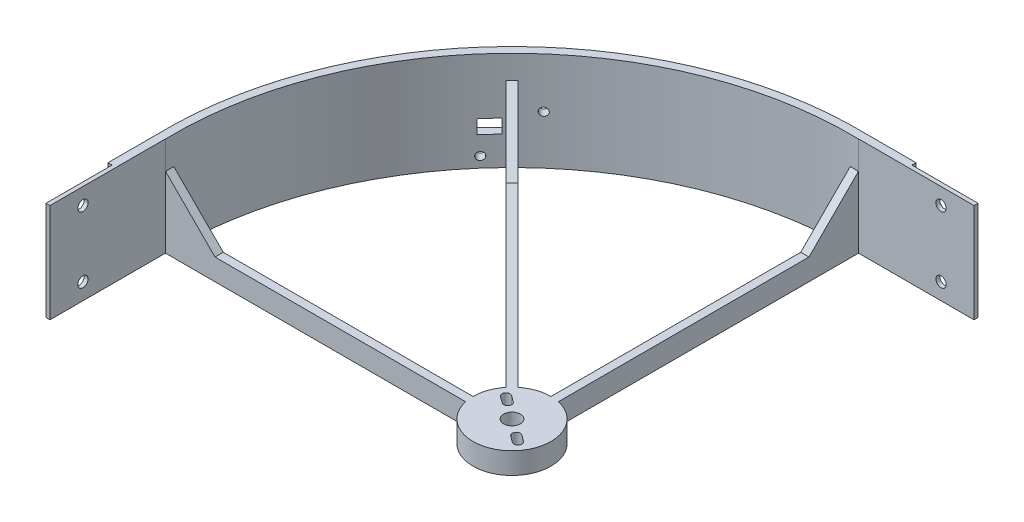
SolidWorks part; units mm, degrees
note: The reader was unsure of these and kept them because the rebuilt part matched: shared geometry of "Sketch1<6>", "Sketch1<7>", "Sketch21<3>".
material "ABS"
ref_plane "Front Plane" through (0, 0, 0) normal (0, 0, 1) x (1, 0, 0)
ref_plane "Top Plane" through (0, 0, 0) normal (0, 1, 0) x (1, 0, 0)
ref_plane "Right Plane" through (0, 0, 0) normal (1, 0, 0) x (0, 0, -1)
sketch "Sketch1" plane through (0, 0, 0) normal (0, 1, 0) x (1, 0, 0)
  line L0 (0, 130.175) -> (0, 9.3426)
  line L1 (3.175, 9.3426) -> (3.175, 130.1363)
  line L2 (-92.0476, 92.0476) -> (0, 0) construction
  line L3 (-90.9182, 93.1633) -> (-5.7657, 8.0107)
  line L4 (-9.7388, -3.175) -> (-130.1363, -3.175)
  line L5 (-130.175, 0) -> (-9.3426, 0)
  line L6 (3.175, 9.3426) -> (3.175, 130.1363)
  line L7 (3.175, 130.1363) -> (3.175, 133.3122)
  line L8 (-130.1363, -3.175) -> (-133.3122, -3.175)
  line L9 (0, 0) -> (-130.175, 0) construction
  line L10 (-8.0089, 5.7638) -> (-93.1633, 90.9182)
  line L11 (0, 0) -> (0, 146.05) construction
  circle A0 centre (0, 0) radius 15
  arc A1 (3.175, 130.1363) -> (-130.1363, -3.175) centre (0, 0) ccw
  arc A2 (3.175, 133.3122) -> (-133.3122, -3.175) centre (0, 0) ccw
  point P21 (0, 0)
  dimension "D1" = 30
  dimension "D2" = 133.35
  dimension "D4" = 3.175
  dimension "D6" = 1.5875
  dimension "D3" = 3.175
  dimension "D7" = 1.5875
  dimension "D5" = 3.175
extrude "Boss-Extrude2" add sketch "Sketch1" along normal blind 8.255 contours A0
extrude "Boss-Extrude3" add sketch "Sketch1<6>" along normal blind 8.255
sketch "Sketch1<6>" plane through (0, 0, 0) normal (0, 1, 0) x (1, 0, 0) same geometry as "Sketch1"
extrude "Boss-Extrude4" add sketch "Sketch1<7>" along normal blind 38.1 contours L7 A2 L8 A1
sketch "Sketch1<7>" plane through (0, 0, 0) normal (0, 1, 0) x (1, 0, 0) same geometry as "Sketch1"
ref_plane "Plane1" through (-63.4806, 0, -63.4806) normal (0.7071, 0, 0.7071) x (0.7071, 0, -0.7071)
sketch "Sketch5" plane through (0, 8.255, 0) normal (0, 1, 0) x (1, 0, 0)
  line L0 (0, 0) -> (-92.0476, 92.0476) construction
  line L1 (0, 0) -> (15.8128, 15.8128) construction
  line L2 (-8.7797, 6.4967) -> (0, 0) construction
  line L3 (-6.3296, 4.6836) -> (-8.7797, 6.4967) construction
  line L4 (-7.2361, 3.4586) -> (-9.6862, 5.2716)
  line L5 (-5.4231, 5.9087) -> (-7.8732, 7.7217)
  line L6 (0, 0) -> (3.6216, 4.8943) construction
  line L7 (6.3296, -4.6836) -> (8.7797, -6.4967) construction
  line L8 (5.4231, -5.9087) -> (7.8732, -7.7217)
  line L9 (7.2361, -3.4586) -> (9.6862, -5.2716)
  line L10 (-90.9182, 93.1633) -> (-9.4245, 11.6696) construction
  arc A0 (5.4231, -5.9087) -> (7.2361, -3.4586) centre (6.3296, -4.6836) cw
  arc A1 (-7.2361, 3.4586) -> (-5.4231, 5.9087) centre (-6.3296, 4.6836) ccw
  arc A2 (-7.8732, 7.7217) -> (-9.6862, 5.2716) centre (-8.7797, 6.4967) ccw
  arc A3 (9.6862, -5.2716) -> (7.8732, -7.7217) centre (8.7797, -6.4967) cw
  circle A6 centre (0, 0) radius 3.25
  point P8 (-7.5546, 5.5901)
  point P17 (7.5546, -5.5901)
  point P18 (0, 0)
  dimension "D3" = 3.048
  dimension "D1" = 7.874
  dimension "D2" = 3.048
  dimension "D4" = 8.5
extrude "Cut-Extrude3" cut sketch "Sketch5" against normal blind 63.5
sketch "Sketch6" plane through (0, 0, 3.175) normal (0, 0, 1) x (1, 0, 0)
  line L0 (-14.6601, 0) -> (-133.3122, 0) construction
  line L1 (-130.1363, 38.1) -> (-131.7242, 38.1)
  line L2 (-130.1363, 38.1) -> (-130.1363, 0)
  line L3 (-130.1363, 0) -> (-131.7242, 0)
  line L4 (-131.7242, 38.1) -> (-131.7242, 0)
  line L5 (-130.1363, 38.1) -> (-133.3122, 38.1) construction
  point P7 (-131.7242, 38.1)
sketch "Sketch7" plane through (3.175, 0, 0) normal (1, 0, 0) x (0, 0, -1)
  line L0 (14.6601, 0) -> (133.3122, 0) construction
  line L1 (130.1363, 38.1) -> (131.7242, 38.1)
  line L2 (130.1363, 38.1) -> (130.1363, 0)
  line L3 (130.1363, 0) -> (131.7242, 0)
  line L4 (131.7242, 38.1) -> (131.7242, 0)
  line L5 (130.1363, 38.1) -> (133.3122, 38.1) construction
  line L6 (130.1363, 38.1) -> (130.1363, 8.255) construction
  point P7 (131.7242, 38.1)
ref_plane "Plane2" through (0, 0, 0) normal (0, 0, -1) x (-1, 0, 0)
sketch "Sketch10" plane through (0, 0, 0) normal (0, 0, -1) x (-1, 0, 0)
  line L0 (130.175, 27.305) -> (130.175, 8.255)
  line L4 (130.175, 8.255) -> (130.175, 38.1) construction
  line L5 (130.175, 8.255) -> (111.125, 8.255)
  line L6 (130.175, 8.255) -> (15, 8.255) construction
  line L7 (111.125, 8.255) -> (130.175, 27.305)
  dimension "D1" = 19.05
  dimension "D2" = 45
extrude "Boss-Extrude9" add sketch "Sketch10" against normal blind 3.175
ref_plane "Plane3" through (1.1225, 0, -1.1225) normal (0.7071, 0, -0.7071) x (-0.7071, 0, -0.7071)
ref_plane "Plane4" through (0, 0, 0) normal (-1, 0, 0) x (0, 0, 1)
sketch "Sketch13" plane through (0, 0, 0) normal (-1, 0, 0) x (0, 0, 1)
  line L0 (-130.175, 27.305) -> (-111.125, 8.255)
  line L1 (-130.175, 27.305) -> (-130.175, 8.255)
  line L2 (-130.175, 8.255) -> (-15, 8.255) construction
  line L3 (-130.175, 8.255) -> (-111.125, 8.255)
  line L4 (-130.175, 38.1) -> (-130.175, 8.255) construction
  dimension "D1" = 45
  dimension "D2" = 19.05
extrude "Boss-Extrude11" add sketch "Sketch13" against normal blind 3.175
sketch "Sketch14" plane through (1.1225, 0, -1.1225) normal (0.7071, 0, -0.7071) x (-0.7071, 0, -0.7071)
  line L0 (133.3403, 8.255) -> (111.1153, 8.255)
  line L1 (130.1653, 8.255) -> (14.9158, 8.255) construction
  line L2 (133.3403, 8.255) -> (133.3403, 32.3947)
  line L3 (133.3403, 32.3947) -> (111.1153, 8.255)
  dimension "D1" = 22.225
extrude "Boss-Extrude14" add sketch "Sketch14" against normal blind 3.175
ref_plane "Plane5" through (-131.7242, 0, 0) normal (-1, 0, 0) x (0, -1, 0)
sketch "Sketch15" plane through (-131.7242, 0, 0) normal (-1, 0, 0) x (0, -1, 0)
  line L1 (-38.1, 47.625) -> (0, 47.625)
  line L2 (-38.1, 47.625) -> (-38.1, 3.175)
  line L3 (-38.1, 3.175) -> (0, 3.175)
  line L4 (0, 47.625) -> (0, 3.175)
  dimension "D1" = 44.45
extrude "Boss-Extrude15" add sketch "Sketch15" against normal blind 1.524
ref_plane "Plane6" through (0, 0, -131.7242) normal (0, 0, -1) x (0, -1, 0)
sketch "Sketch16" plane through (0, 0, -131.7242) normal (0, 0, -1) x (0, -1, 0)
  line L1 (-38.1, -3.175) -> (0, -3.175)
  line L2 (-38.1, -3.175) -> (-38.1, -47.625)
  line L3 (-38.1, -47.625) -> (0, -47.625)
  line L4 (0, -3.175) -> (0, -47.625)
  dimension "D1" = 44.45
extrude "Boss-Extrude16" add sketch "Sketch16" against normal blind 1.524
sketch "Sketch17" plane through (0, 0, -131.7242) normal (0, 0, -1) x (-1, 0, 0)
  line L1 (-3.175, 38.1) -> (-47.625, 38.1) construction
  line L2 (19.05, 19.05) -> (-47.625, 19.05) construction
  line L3 (-47.625, 38.1) -> (-47.625, 0) construction
  circle A0 centre (-34.925, 31.75) radius 1.985
  circle A1 centre (-34.925, 6.35) radius 1.985
  dimension "D1" = 12.7
  dimension "D3" = 3.97
  dimension "D2" = 6.35
extrude "Cut-Extrude4" cut sketch "Sketch17" against normal blind 2.54
sketch "Sketch18" plane through (-131.7242, 0, 0) normal (-1, 0, 0) x (0, 0, 1)
  line L1 (25.4, 19.05) -> (47.625, 19.05) construction
  line L2 (47.625, 0) -> (47.625, 38.1) construction
  line L3 (47.625, 0) -> (47.625, 38.1) construction
  circle A0 centre (34.925, 31.75) radius 1.985
  circle A1 centre (34.925, 6.35) radius 1.985
  dimension "D1" = 3.97
  dimension "D2" = 12.7
  dimension "D3" = 12.7
extrude "Cut-Extrude5" cut sketch "Sketch18" against normal blind 2.54
sketch "Sketch19" plane through (-131.7242, 0, 0) normal (-1, 0, 0) x (0, 0, 1)
  line L0 (3.175, 0) -> (47.625, 0) construction
  line L1 (3.175, 38.1) -> (22.225, 38.1)
  line L2 (3.175, 38.1) -> (3.175, 0)
  line L3 (3.175, 0) -> (22.225, 0)
  line L4 (22.225, 38.1) -> (22.225, 0)
  dimension "D1" = 19.05
extrude "Boss-Extrude17" add sketch "Sketch19" along normal up to vertex (1.588 mm away)
sketch "Sketch20" plane through (0, 0, -131.7242) normal (0, 0, -1) x (-1, 0, 0)
  line L0 (-47.625, 0) -> (-3.175, 0) construction
  line L1 (-3.175, 38.1) -> (-22.225, 38.1)
  line L2 (-3.175, 38.1) -> (-3.175, 0)
  line L3 (-3.175, 0) -> (-22.225, 0)
  line L4 (-22.225, 38.1) -> (-22.225, 0)
  dimension "D1" = 19.05
extrude "Boss-Extrude18" add sketch "Sketch20" along normal up to vertex (1.588 mm away)
ref_plane "Plane7" through (-94.2927, 0, -94.2927) normal (-0.7071, 0, -0.7071) x (-0.7071, 0, 0.7071)
sketch "Sketch21" plane through (-94.2927, 0, -94.2927) normal (-0.7071, 0, -0.7071) x (-0.7071, 0, 0.7071)
  line L0 (-12.7, 0) -> (12.7, 0)
  line L1 (12.7, 0) -> (12.7, 22.86)
  line L2 (12.7, 22.86) -> (-12.7, 22.86)
  line L3 (0, 0) -> (0, 28.774) construction
  line L4 (-12.7, 0) -> (-12.7, 22.86)
  circle A0 centre (8.636, 4.064) radius 1.524
  circle A1 centre (-8.636, 18.796) radius 1.524
  point P8 (0, 22.86)
  dimension "D3" = 3.048
  dimension "D6" = 3.048
  dimension "D1" = 12.7
  dimension "D2" = 22.86
  dimension "D4" = 4.064
  dimension "D5" = 4.064
  dimension "D7" = 4.064
  dimension "D8" = 4.064
extrude "Cut-Extrude6" cut sketch "Sketch21" against normal up to surface (3.3694 mm away) contours A1 | A0
extrude "Boss-Extrude20" add sketch "Sketch21<3>" against normal up to surface up to face at (-99.2147, 4.4138, -89.0992)
sketch "Sketch21<3>" plane through (-94.2927, 0, -94.2927) normal (-0.7071, 0, -0.7071) x (-0.7071, 0, 0.7071) same geometry as "Sketch21"
sketch "Sketch26" plane through (-94.2927, 0, -94.2927) normal (-0.7071, 0, -0.7071) x (-0.7071, 0, 0.7071)
  line L0 (12.7, 22.86) -> (0, 22.86) construction
  line L1 (2.667, 16.51) -> (9.525, 16.51)
  line L2 (2.667, 16.51) -> (2.667, 11.176)
  line L3 (2.667, 11.176) -> (9.525, 11.176)
  line L4 (9.525, 16.51) -> (9.525, 11.176)
  line L5 (12.7, 0) -> (12.7, 22.86) construction
  dimension "D1" = 6.35
  dimension "D2" = 3.175
  dimension "D3" = 6.858
  dimension "D4" = 5.334
extrude "Cut-Extrude7" cut sketch "Sketch26" against normal up to surface (3.5239 mm away)
